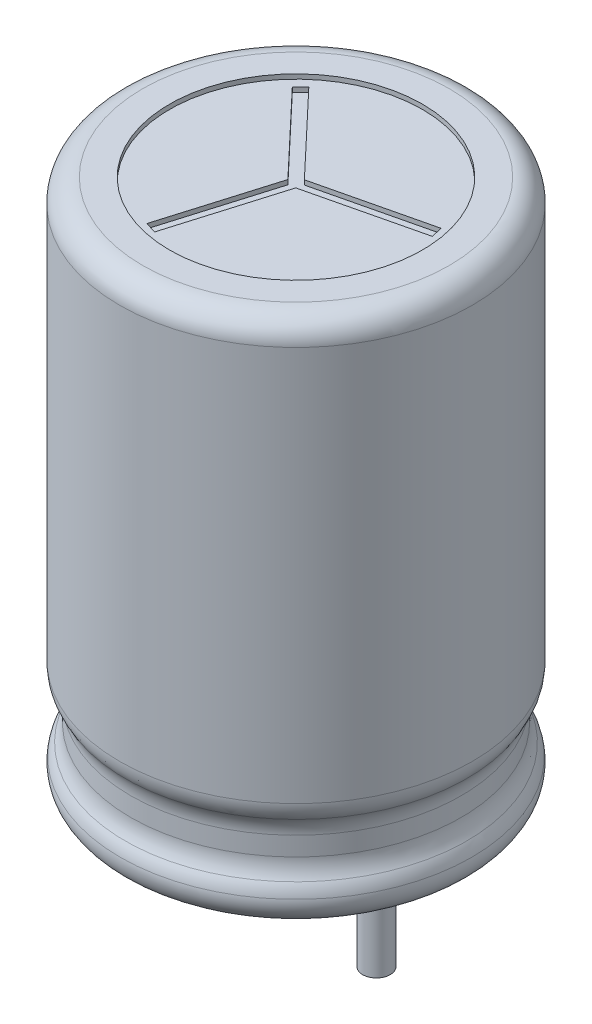
SolidWorks part; units mm, degrees
ref_plane "Front Plane" through (0, 0, 0) normal (0, 0, 1) x (1, 0, 0)
ref_plane "Top Plane" through (0, 0, 0) normal (0, 1, 0) x (1, 0, 0)
ref_plane "Right Plane" through (0, 0, 0) normal (1, 0, 0) x (0, 0, -1)
sketch "Sketch1" plane through (0, 0, 0) normal (0, 0, 1) x (1, 0, 0)
  line L0 (3.8333, 11.5) -> (0, 11.5)
  line L1 (0, 11.5) -> (0, 0)
  line L2 (0, 0) -> (3.6439, 0)
  line L3 (3.5937, 1.2326) -> (3.5937, 1.6424)
  line L4 (3.8333, 2.4076) -> (3.8333, 11.5)
  line L5 (0, 11.5) -> (0, 0) construction
  arc A0 (3.6439, 0) -> (3.7136, 0.8499) centre (3.1626, 0.4673) ccw
  arc A1 (3.7136, 0.8499) -> (3.5937, 1.2326) centre (4.2646, 1.2326) cw
  arc A2 (3.5937, 1.6424) -> (3.7135, 2.025) centre (4.2646, 1.6424) cw
  arc A3 (3.7135, 2.025) -> (3.8333, 2.4076) centre (3.1625, 2.4076) ccw
  dimension "D1" = 11.5
revolve "Revolve1" add sketch "Sketch1" angle 360 about L5 reverse direction yes
sketch "Sketch2" plane through (0, 11.5, 0) normal (0, 1, 0) x (-1, 0, 0)
  circle A0 centre (0, 0) radius 2.75
extrude "Cut-Extrude1" cut sketch "Sketch2" against normal blind 0.1
sketch "Sketch3" plane through (0, 11.4, 0) normal (0, 1, 0) x (-1, 0, 0)
  line L0 (1.6535, -1.9323) -> (1.838, -1.7577)
  line L1 (1.838, -1.7577) -> (0.1426, 0.034)
  line L2 (0.1426, 0.034) -> (0.8467, 2.3981)
  line L3 (0.8467, 2.3981) -> (0.6032, 2.4706)
  line L4 (0.6032, 2.4706) -> (-0.1008, 0.1065)
  line L5 (-0.1008, 0.1065) -> (-2.5002, -0.4658)
  line L6 (-2.5002, -0.4658) -> (-2.4412, -0.7129)
  line L7 (-2.4412, -0.7129) -> (-0.0419, -0.1405)
  line L8 (-0.0419, -0.1405) -> (1.6535, -1.9323)
extrude "Cut-Extrude2" cut sketch "Sketch3" against normal blind 0.1
ref_plane "Plane1" through (0, 0, 0) normal (0, 0, -1) x (-1, 0, 0)
sketch "Sketch4" plane through (0, 0, 0) normal (0, 0, -1) x (-1, 0, 0)
  line L0 (-2.05, -2.5) -> (-1.75, -2.5)
  line L1 (-1.75, -2.5) -> (-1.75, 0)
  line L2 (-1.75, 0) -> (-2.05, 0)
  line L3 (-2.05, 0) -> (-2.05, -2.5)
  line L4 (-1.75, -2.5) -> (-1.75, 0) construction
revolve "Revolve2" add sketch "Sketch4" angle 360 about L4 reverse direction yes
sketch "Sketch5" plane through (0, 0, 0) normal (0, 0, -1) x (-1, 0, 0)
  line L0 (1.45, -2.5) -> (1.75, -2.5)
  line L1 (1.75, -2.5) -> (1.75, 0)
  line L2 (1.75, 0) -> (1.45, 0)
  line L3 (1.45, 0) -> (1.45, -2.5)
  line L4 (1.75, -2.5) -> (1.75, 0) construction
revolve "Revolve3" add sketch "Sketch5" angle 360 about L4 reverse direction yes
fillet "Fillet1" radius 0.5 2 edges at (0, 11.5, -3.8333) (0, 0, -3.6439) tangent propagation no
